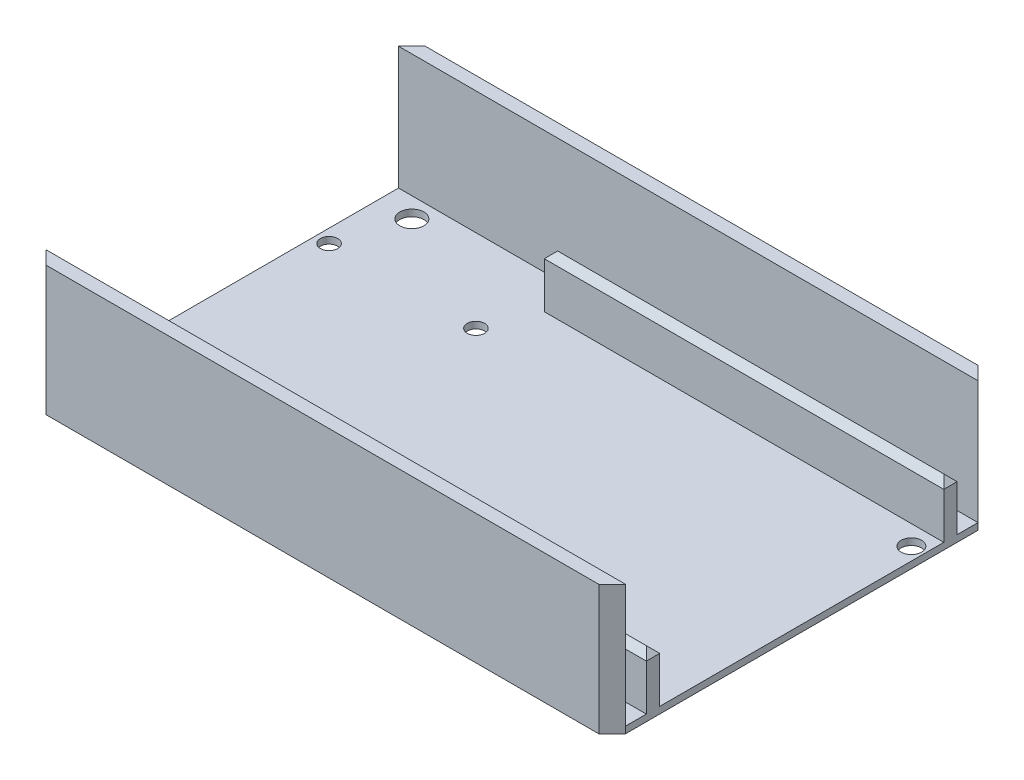
SolidWorks part; units mm, degrees
ref_plane "Front Plane" through (0, 0, 0) normal (0, 0, 1) x (1, 0, 0)
ref_plane "Top Plane" through (0, 0, 0) normal (0, 1, 0) x (1, 0, 0)
ref_plane "Right Plane" through (0, 0, 0) normal (1, 0, 0) x (0, 0, -1)
sketch "Sketch1" plane through (0, 0, 0) normal (0, 1, 0) x (1, 0, 0)
  line L1 (0, 0) -> (110.236, 0)
  line L2 (0, 0) -> (0, 72.136)
  line L3 (0, 72.136) -> (110.236, 72.136)
  line L4 (110.236, 0) -> (110.236, 72.136)
  dimension "D1" = 110.236
  dimension "D2" = 72.136
extrude "Radio Mount Plate" add sketch "Sketch1" along normal blind 1.27
sketch "Sketch2" plane through (0, 1.27, 0) normal (0, 1, 0) x (1, 0, 0)
  line L0 (0, 72.136) -> (0, 0) construction
  line L1 (34.236, 61.818) -> (110.236, 61.818) construction
  line L2 (34.236, 61.818) -> (34.236, 10.318) construction
  line L3 (34.236, 10.318) -> (110.236, 10.318) construction
  line L4 (110.236, 61.818) -> (110.236, 10.318) construction
  line L6 (110.236, 0) -> (110.236, 72.136) construction
  line L8 (0, 56.388) -> (33.02, 56.388) construction
  line L9 (0, 56.388) -> (0, 15.748) construction
  line L10 (0, 15.748) -> (33.02, 15.748) construction
  line L11 (33.02, 56.388) -> (33.02, 15.748) construction
  line L13 (33.02, 36.068) -> (34.236, 36.068) construction
  line L14 (2.54, 53.848) -> (30.48, 53.848) construction
  line L15 (30.48, 53.848) -> (30.48, 18.288) construction
  circle A0 centre (107.786, 59.368) radius 1.95
  circle A1 centre (38.036, 17.318) radius 1.95
  circle A2 centre (2.54, 53.848) radius 1.651
  circle A3 centre (30.48, 53.848) radius 1.651
  circle A4 centre (30.48, 18.288) radius 1.651
  circle A5 centre (2.54, 18.288) radius 1.651
  point P4 (34.236, 36.068)
  point P7 (0, 36.068)
  point P15 (0, 36.068)
  point P18 (0, 0)
  point P31 (30.48, 36.068)
  point P32 (16.51, 53.848)
  point P33 (16.51, 56.388)
  dimension "D5" = 3.9
  dimension "D6" = 7
  dimension "D7" = 3.8
  dimension "D8" = 2.45
  dimension "D9" = 2.45
  dimension "D11" = 35.56
  dimension "D12" = 3.302
  dimension "D1" = 51.5
  dimension "D2" = 76
  dimension "D3" = 33.02
  dimension "D4" = 40.64
  dimension "D10" = 27.94
extrude "Cut-Extrude1" cut sketch "Sketch2" against normal through all
sketch "Sketch3" plane through (0, 1.27, 0) normal (0, 1, 0) x (1, 0, 0)
  line L0 (110.236, 0) -> (110.236, 72.136) construction
  line L1 (0, 72.136) -> (110.236, 72.136)
  line L2 (0, 72.136) -> (0, 69.596)
  line L3 (0, 69.596) -> (110.236, 69.596)
  line L4 (110.236, 72.136) -> (110.236, 69.596)
  line L5 (0, 72.136) -> (0, 0) construction
  line L6 (110.236, 0) -> (0, 0)
  line L7 (110.236, 0) -> (110.236, 2.54)
  line L8 (110.236, 2.54) -> (0, 2.54)
  line L9 (0, 0) -> (0, 2.54)
  dimension "D1" = 2.54
extrude "Boss-Extrude2" add sketch "Sketch3" along normal blind 23.3705
sketch "Sketch4" plane through (0, 1.27, 0) normal (0, 1, 0) x (1, 0, 0)
  line L0 (-1000, 36.068) -> (49000, 36.068) construction
  line L2 (0, 69.596) -> (0, 2.54) construction
  line L3 (0, 69.596) -> (110.236, 69.596) construction
  circle A1 centre (6.35, 65.786) radius 2.286
  circle A3 centre (6.35, 6.35) radius 2.286
  dimension "D1" = 4.572
  dimension "D3" = 6.35
  dimension "D4" = 3.81
extrude "Cut-Extrude2" cut sketch "Sketch4" against normal through all
sketch "Sketch5" plane through (0, 1.27, 0) normal (0, 1, 0) x (1, 0, 0)
  line L0 (34.236, 61.818) -> (110.236, 61.818) construction
  line L1 (34.236, 65.628) -> (110.236, 65.628)
  line L2 (34.236, 65.628) -> (34.236, 63.088)
  line L3 (34.236, 63.088) -> (110.236, 63.088)
  line L4 (110.236, 65.628) -> (110.236, 63.088)
  line L5 (34.236, 9.048) -> (110.236, 9.048)
  line L6 (34.236, 9.048) -> (34.236, 6.508)
  line L7 (34.236, 6.508) -> (110.236, 6.508)
  line L8 (110.236, 9.048) -> (110.236, 6.508)
  line L9 (34.236, 10.318) -> (110.236, 10.318) construction
  line L10 (110.236, 61.818) -> (110.236, 10.318) construction
  line L11 (34.236, 61.818) -> (34.236, 10.318) construction
  dimension "D1" = 1.27
  dimension "D2" = 1.27
  dimension "D3" = 2.54
extrude "Boss-Extrude3" add sketch "Sketch5" along normal blind 10
chamfer "Chamfer1" distance 1.27 angle 45 8 edges at (72.236, 11.27, -65.628) (110.236, 11.27, -64.358) (72.236, 11.27, -63.088) (34.236, 11.27, -64.358) (72.236, 11.27, -9.048) (110.236, 11.27, -7.778) (72.236, 11.27, -6.508) (34.236, 11.27, -7.778)
chamfer "Chamfer2" distance 2.54 angle 45 4 edges at (110.236, 12.3203, 0) (110.236, 12.3203, -72.136) (0, 12.3203, -72.136) (0, 12.3203, 0)
